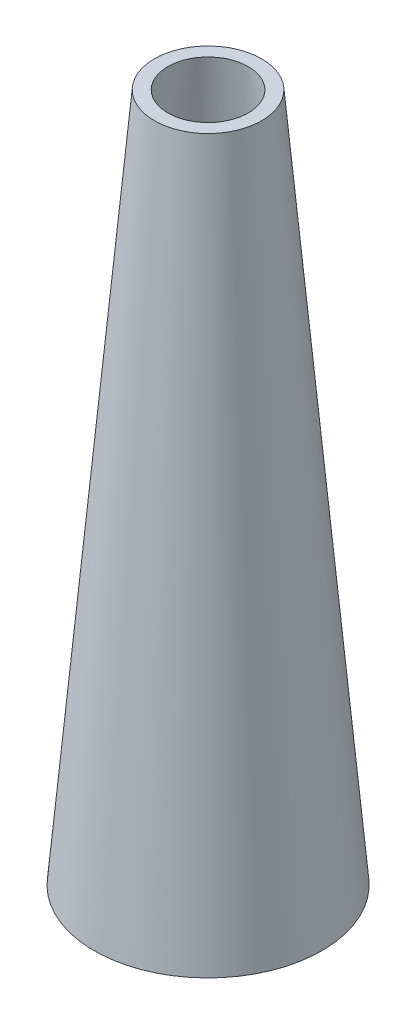
SolidWorks part; units mm, degrees
material "S-Glass Fiber"
ref_plane "Front Plane" through (0, 0, 0) normal (0, 0, 1) x (1, 0, 0)
ref_plane "Top Plane" through (0, 0, 0) normal (0, 1, 0) x (1, 0, 0)
ref_plane "Right Plane" through (0, 0, 0) normal (1, 0, 0) x (0, 0, -1)
sketch "Sketch1" plane through (0, 0, 0) normal (0, 0, 1) x (1, 0, 0)
  line L0 (0, 0) -> (0, 43.3348) construction
  line L1 (9.525, 43.3348) -> (12.7121, 43.3348)
  line L2 (12.7121, 43.3348) -> (26.9875, -119.8334)
  line L3 (26.9875, -119.8334) -> (23.8004, -119.8334)
  line L4 (23.8004, -119.8334) -> (9.525, 43.3348)
  point P5 (9.525, 43.3348)
  point P8 (12.7121, 43.3348)
  point P11 (23.8004, -119.8334)
revolve "Revolve1" add sketch "Sketch1" angle 360 about L0
